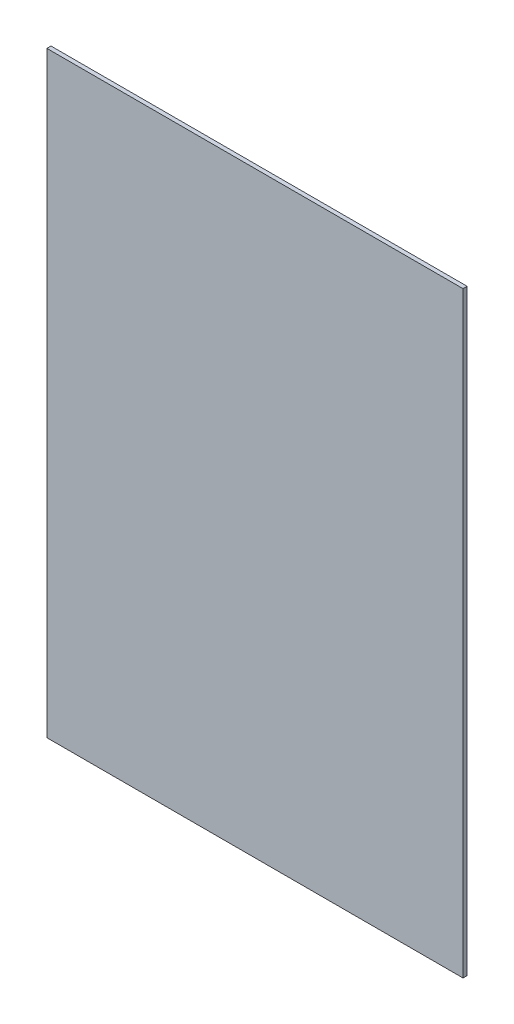
SolidWorks part; units mm, degrees
ref_plane "Спереди" through (0, 0, 0) normal (0, 0, 1) x (1, 0, 0)
ref_plane "Сверху" through (0, 0, 0) normal (0, 1, 0) x (1, 0, 0)
ref_plane "Справа" through (0, 0, 0) normal (1, 0, 0) x (0, 0, -1)
other "Configuration Table"
sketch "Эскиз2" plane through (0, 0, 0) normal (0, 0, 1) x (1, 0, 0)
  line L1 (1138.3, -436.3) -> (530, -436.3)
  line L2 (1138.3, -436.3) -> (1138.3, 436.3)
  line L3 (1138.3, 436.3) -> (530, 436.3)
  line L11 (530, -436.3) -> (530, 436.3)
  line L15 (530, 394.3) -> (530, 430.3) construction
  line L16 (1138.3, 436.3) -> (524, 436.3) construction
  point P5 (0, 0)
  point P8 (0, 0)
extrude "Бобышка-Вытянуть1" add sketch "Эскиз2" against normal blind 6
equation "\"Ширина груза\"= 420"
equation "\"Глубина груза\"= 490"
equation "\"Высота груза\"= 297"
equation "\"Ширина ячейки\"= \"Ширина груза\" + 10"
equation "\"Глубина ячейки\"= \"Глубина груза\" + 10"
equation "\"Высота ячейки\"= \"Высота груза\" + 10 + 13"
equation "\"Колво ячеек ширина\"= 2"
equation "\"Колво ячеек высота\"= 2"
equation "\"Толщина стенки\" = 6"
equation "\"Крепление дверцы\"= 5"
equation "\"Ширина рейки\"= \"Толщина шестерни\""
equation "\"Высота рейки\"= 20"
equation "\"Высота пола\"= 20"
equation "\"Колво полозьев\"= 5"
equation "\"Отступ рейки\"= 20"
equation "\"Глубина каретки\"= \"Глубина ячейки\" + 30 + \"Мотор Y высота корпуса\" + 20"
equation "\"Длинна рейки\"= ( \"Ширина ячейки\" + \"Толщина стенки\" + \"Крепление дверцы\" ) * \"Колво ячеек ширина\" + \"Ширина ячейки выгрузки\" * \"Колво выгрузки\" + \"Толщина стенки\""
equation "\"Отступ шпильки\"= 26"
equation "\"Диаметр шпильки\"= 5"
equation "\"Длинна шпильки\"= ( \"Высота ячейки\" + \"Толщина стенки\" + \"Высота пола\" ) * \"Колво ячеек высота\" + ( \"Толщина стенки\" + \"Отступ рейки\" ) * 2 "
equation "\"Ширина пластины\"= 50  "
equation "\"Высота зона выгрузки\"= \"Высота ячейки\" * 2 + \"Толщина стенки\" * 2"
equation "\"Колво выгрузки\"= 1"
equation "\"Ширина ячейки выгрузки\"= \"Ширина ячейки\" + \"Толщина стенки\" + \"Отступ крепления мотора фиксации\"*2"
equation "\"Отступ крепления мотора фиксации\" = 30"
equation "\"Мотор X ширина корпуса\"= 42.3"
equation "\"Мотор X высота корпуса\"= 42.3"
equation "\"Мотор X длина корпуса\"= 40"
equation "\"Мотор X вылет вала\"= 19.8"
equation "\"Мотор Y ширина корпуса\"= 42.3"
equation "\"Мотор Y высота корпуса\"= 42.3"
equation "\"Мотор Y длина корпуса\"= 48"
equation "\"Мотор Y вылет вала\"= 30"
equation "\"Мотор Z ширина корпуса\"= 42"
equation "\"Мотор Z высота корпуса\"= 42"
equation "\"Мотор Z длина корпуса\"= 40"
equation "\"Мотор Z вылет вала\"= 23"
equation "\"Мотор диаметр вала ПРЕДВ\"= 5"
equation "\"Мотор шаг крепления ПРЕДВ\"= 31"
equation "\"Мотор диаметр отверстий ПРЕДВ\"= 3"
equation "\"Мотор глубина отверстий ПРЕДВ\"= 4.5"
equation "\"Мотор диаметр буртика ПРЕДВ\"= 22"
equation "\"Мотор высота буртика ПРЕДВ\"= 2"
equation "\"Мотор диаметр шкива ПРЕДВ\"= 16"
equation "\"Мотор длина шкива ПРЕДВ\"= 12"
equation "\"Мотор отступ шкива ПРЕДВ\"= 5"
equation "\"Мотор X шаг градусов\"= 1.8"
equation "\"Мотор Y шаг градусов\"= 1.8"
equation "\"Мотор Z шаг градусов\"= 1.8"
equation "\"Мотор Y диаметр ротора\"= 25.78"
equation "\"Толщина шестерни\"= 10"
equation "\"D1@Бобышка-Вытянуть1\"=\"Толщина стенки\""
